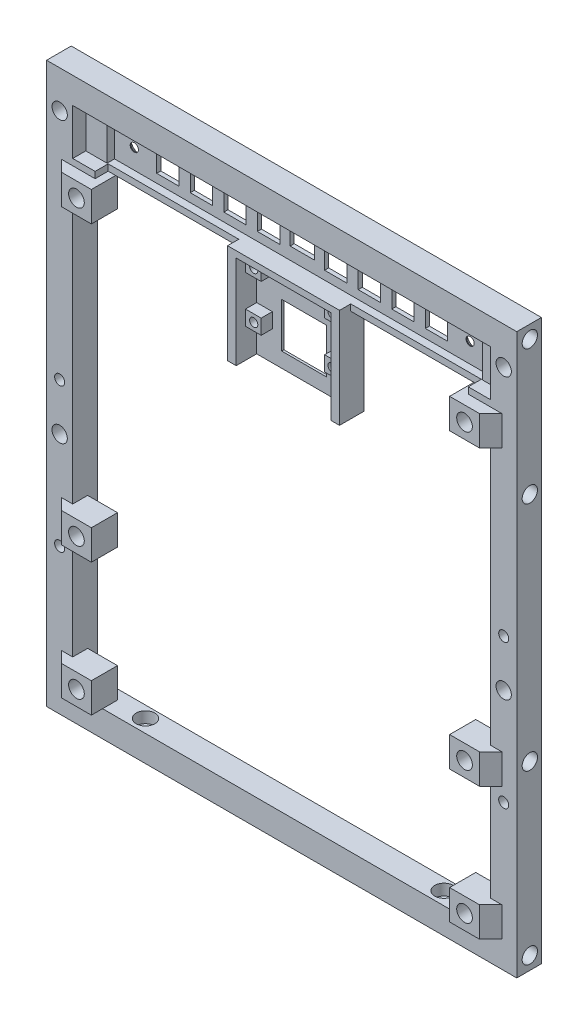
SolidWorks part; units mm, degrees
ref_plane "Front Plane" through (0, 0, 0) normal (0, 0, 1) x (1, 0, 0)
ref_plane "Top Plane" through (0, 0, 0) normal (0, 1, 0) x (1, 0, 0)
ref_plane "Right Plane" through (0, 0, 0) normal (1, 0, 0) x (0, 0, -1)
sketch "Sketch1" plane through (0, 0, 0) normal (0, 0, 1) x (1, 0, 0)
  line L1 (-63, -75) -> (63, -75)
  line L2 (-63, -75) -> (-63, 75)
  line L3 (-63, 75) -> (63, 75)
  line L4 (63, -75) -> (63, 75)
  line L5 (-63, -75) -> (63, 75) construction
  line L6 (-63, 75) -> (63, -75) construction
  line L7 (-56, -68) -> (56, -68)
  line L8 (-56, -68) -> (-56, 68)
  line L9 (-56, 68) -> (56, 68)
  line L10 (56, -68) -> (56, 68)
  line L11 (-56, -68) -> (56, 68) construction
  line L12 (-56, 68) -> (56, -68) construction
  point P0 (0, 0)
  point P6 (0, 0)
  dimension "D1" = 126
  dimension "D2" = 150
  dimension "D3" = 7
  dimension "D4" = 7
extrude "Boss-Extrude1" add sketch "Sketch1" along normal blind 7
sketch "Sketch2" plane through (-63, 0, 0) normal (-1, 0, 0) x (0, 0, 1)
  line L0 (3.5, 71.5) -> (3.5, -71.5) construction
  line L1 (7, 75) -> (0, 75) construction
  circle A0 centre (3.5, -71.5) radius 2.05
  circle A2 centre (3.5, 71.5) radius 2.05
  circle A3 centre (3.5, 35.5) radius 2.05
  circle A4 centre (3.5, -26.5) radius 2.05
  point P2 (3.5, 0)
  point P7 (3.5, 75)
  dimension "D2" = 4.1
  dimension "D3" = 36
  dimension "D4" = 45
  dimension "D1" = 3.5
extrude "Cut-Extrude1" cut sketch "Sketch2" against normal blind 6
mirror "Mirror1" about plane through (0, 0, 0) normal (1, 0, 0) of "Cut-Extrude1"
sketch "Sketch3" plane through (0, -68, 0) normal (0, 1, 0) x (1, 0, 0)
  line L0 (0, 0) -> (0, -7) construction
  line L1 (-56, 0) -> (56, 0) construction
  line L2 (-56, -7) -> (56, -7) construction
  line L3 (40, -3.5) -> (-40, -3.5) construction
  circle A0 centre (40, -3.5) radius 1.35
  circle A1 centre (-40, -3.5) radius 1.35
  point P9 (0, -3.5)
  dimension "D1" = 2.7
  dimension "D2" = 80
extrude "Cut-Extrude2" cut sketch "Sketch3" against normal through all
sketch "Sketch4" plane through (0, -68, 0) normal (0, 1, 0) x (1, 0, 0)
  circle A0 centre (40, -3.5) radius 2.5
  circle A1 centre (-40, -3.5) radius 2.5
  dimension "D1" = 5
extrude "Cut-Extrude3" cut sketch "Sketch4" against normal blind 3
sketch "Sketch5" plane through (0, 0, 0) normal (0, 0, -1) x (-1, 0, 0)
  line L0 (-59.5, -75) -> (-59.5, 75) construction
  line L1 (63, -75) -> (-63, -75) construction
  line L2 (-63, 75) -> (63, 75) construction
  line L3 (-56, 0) -> (-63, 0) construction
  line L4 (-56, -68) -> (-56, 68) construction
  line L5 (-63, -75) -> (-63, 75) construction
  line L6 (0, 75) -> (0, -75) construction
  line L7 (56, -68) -> (-56, -68) construction
  circle A0 centre (-59.5, 2.6) radius 1.35
  circle A1 centre (59.5, 2.6) radius 1.35
  circle A2 centre (-59.5, -36) radius 1.35
  circle A3 centre (59.5, -36) radius 1.35
  point P12 (-59.5, 0)
  point P13 (-59.5, 0)
  dimension "D1" = 2.7
  dimension "D2" = 2.6
  dimension "D3" = 32
extrude "Cut-Extrude4" cut sketch "Sketch5" against normal through all
sketch "Sketch6" plane through (0, 0, 0) normal (0, 0, -1) x (-1, 0, 0)
  circle A0 centre (-59.5, 2.6) radius 2.5
  circle A1 centre (59.5, 2.6) radius 2.5
  circle A2 centre (-59.5, -36) radius 2.5
  circle A3 centre (59.5, -36) radius 2.5
  dimension "D1" = 5
extrude "Cut-Extrude5" cut sketch "Sketch6" against normal blind 3
sketch "Sketch7" plane through (0, 0, 0) normal (0, 0, -1) x (-1, 0, 0)
  line L0 (-56, 68) -> (-63, 68) construction
  line L1 (-63, -75) -> (-63, 75) construction
  line L2 (-59.5, 65) -> (-59.5, -10) construction
  line L3 (-63, 75) -> (63, 75) construction
  circle A0 centre (-59.5, 65) radius 2.05
  circle A1 centre (-59.5, -10) radius 2.05
  point P8 (-59.5, 68)
  dimension "D1" = 4.1
  dimension "D2" = 10
  dimension "D3" = 75
extrude "Cut-Extrude6" cut sketch "Sketch7" against normal through all
mirror "Mirror2" about plane through (0, 0, 0) normal (1, 0, 0) of "Cut-Extrude6"
sketch "Sketch8" plane through (0, 0, 3) normal (0, 0, -1) x (-1, 0, 0)
  line L2 (-60.85, 0.4958) -> (-60.85, 4.7042)
  line L4 (-58.15, 0.4958) -> (-58.15, 4.7042)
  line L5 (-60.85, 0.4958) -> (-58.15, 4.7042) construction
  line L6 (-60.85, 4.7042) -> (-58.15, 0.4958) construction
  line L8 (-60.85, -38.1042) -> (-60.85, -33.8958)
  line L10 (-58.15, -38.1042) -> (-58.15, -33.8958)
  line L11 (-60.85, -38.1042) -> (-58.15, -33.8958) construction
  line L12 (-60.85, -33.8958) -> (-58.15, -38.1042) construction
  circle A0 centre (-59.5, 2.6) radius 2.5 construction
  circle A1 centre (-59.5, -36) radius 2.5 construction
  circle A2 centre (-59.5, -36) radius 2.5 construction
  arc A3 (-58.15, 4.7042) -> (-60.85, 4.7042) centre (-59.5, 2.6) ccw
  arc A4 (-58.15, -33.8958) -> (-60.85, -33.8958) centre (-59.5, -36) ccw
  circle A5 centre (-59.5, 2.6) radius 1.35 construction
  circle A6 centre (-59.5, -36) radius 1.35 construction
  arc A7 (-60.85, -38.1042) -> (-58.15, -38.1042) centre (-59.5, -36) ccw
  arc A8 (-60.85, 0.4958) -> (-58.15, 0.4958) centre (-59.5, 2.6) ccw
  point P0 (-59.5, 2.6)
  point P8 (-59.5, -36)
extrude "Cut-Extrude7" cut sketch "Sketch8" against normal blind 0.2
sketch "Sketch9" plane through (0, 0, 3.2) normal (0, 0, -1) x (-1, 0, 0)
  line L0 (-58.15, 2.6) -> (-58.15, 4.7042) construction
  line L1 (-60.85, 1.25) -> (-58.15, 1.25)
  line L2 (-60.85, 1.25) -> (-60.85, 3.95)
  line L3 (-60.85, 3.95) -> (-58.15, 3.95)
  line L4 (-58.15, 1.25) -> (-58.15, 3.95)
  line L5 (-60.85, 1.25) -> (-58.15, 3.95) construction
  line L6 (-60.85, 3.95) -> (-58.15, 1.25) construction
  line L7 (-58.15, -38.1042) -> (-58.15, -33.8958) construction
  line L8 (-60.85, -37.35) -> (-58.15, -37.35)
  line L9 (-60.85, -37.35) -> (-60.85, -34.65)
  line L10 (-60.85, -34.65) -> (-58.15, -34.65)
  line L11 (-58.15, -37.35) -> (-58.15, -34.65)
  line L12 (-60.85, -37.35) -> (-58.15, -34.65) construction
  line L13 (-60.85, -34.65) -> (-58.15, -37.35) construction
  arc A0 (-58.15, 2.6) -> (-60.85, 2.6) centre (-59.5, 2.6) ccw construction
  point P0 (-59.5, 2.6)
  point P8 (-59.5, -36)
extrude "Cut-Extrude8" cut sketch "Sketch9" against normal blind 0.2
mirror "Mirror3" about plane through (0, 0, 0) normal (1, 0, 0) of "Cut-Extrude8", "Cut-Extrude7"
sketch "Sketch10" plane through (0, 0, 7) normal (0, 0, 1) x (1, 0, 0)
  line L0 (56, -68) -> (56, 68) construction
  line L1 (56, -68) -> (50, -68)
  line L2 (56, -68) -> (56, -62)
  line L3 (56, -62) -> (50, -62)
  line L4 (50, -68) -> (50, -62)
  line L5 (56, -38.5) -> (50, -38.5)
  line L6 (56, -38.5) -> (56, -32.5)
  line L7 (56, -32.5) -> (50, -32.5)
  line L8 (50, -38.5) -> (50, -32.5)
  line L9 (-56, -68) -> (56, -68) construction
  dimension "D1" = 6
  dimension "D2" = 35.5
extrude "Boss-Extrude2" add sketch "Sketch10" against normal offset from surface (5.5 mm away) 1.5 up to face at (-57.45, -10, 0)
sketch "Sketch11" plane through (0, 0, 1.5) normal (0, 0, -1) x (-1, 0, 0)
  line L0 (-56, -38.5) -> (-50, -32.5) construction
  line L2 (-56, -68) -> (-50, -62) construction
  circle A0 centre (-53, -35.5) radius 1.65
  circle A1 centre (-53, -65) radius 1.65
  dimension "D1" = 3.3
extrude "Cut-Extrude9" cut sketch "Sketch11" against normal through all
mirror "Mirror4" about plane through (0, 0, 0) normal (1, 0, 0) of "Cut-Extrude9", "Boss-Extrude2"
sketch "Sketch12" plane through (0, 0, 0) normal (0, 0, -1) x (-1, 0, 0)
  line L0 (56, 68) -> (56, -68) construction
  line L1 (-56, 68) -> (56, 68)
  line L2 (-56, 68) -> (-56, 54)
  line L3 (-56, 54) -> (56, 54)
  line L4 (56, 68) -> (56, 54)
  dimension "D1" = 14
extrude "Boss-Extrude3" add sketch "Sketch12" against normal blind 1.5
sketch "Sketch13" plane through (0, 0, 1.5) normal (0, 0, 1) x (1, 0, 0)
  line L0 (-56, 68) -> (56, 54) construction
  line L2 (-50.3, 55.7) -> (50.3, 55.7)
  line L3 (-50.3, 55.7) -> (-50.3, 66.3)
  line L4 (-50.3, 66.3) -> (50.3, 66.3)
  line L5 (50.3, 55.7) -> (50.3, 66.3)
  line L6 (-50.3, 55.7) -> (50.3, 66.3) construction
  line L7 (-50.3, 66.3) -> (50.3, 55.7) construction
  line L8 (-56, 54) -> (56, 54)
  line L9 (-56, 54) -> (-56, 68)
  line L10 (-56, 68) -> (56, 68)
  line L11 (56, 54) -> (56, 68)
  line L12 (-56, 54) -> (56, 68) construction
  line L13 (-56, 68) -> (56, 54) construction
  point P4 (0, 61)
  point P9 (0, 61)
  dimension "D1" = 100.6
  dimension "D2" = 10.6
extrude "Boss-Extrude4" add sketch "Sketch13" along normal blind 2
sketch "Sketch14" plane through (0, 0, 1.5) normal (0, 0, 1) x (1, 0, 0)
  line L0 (0, 66.3) -> (0, 55.7) construction
  line L1 (50.3, 66.3) -> (-50.3, 66.3) construction
  line L2 (-50.3, 55.7) -> (50.3, 55.7) construction
  line L3 (-50.3, 61) -> (50.3, 61) construction
  line L4 (50.3, 55.7) -> (50.3, 66.3) construction
  line L5 (-33, 64) -> (-39, 64)
  line L6 (-3.25, 59) -> (3.25, 59)
  line L7 (-3.25, 59) -> (-3.25, 63)
  line L8 (-3.25, 63) -> (3.25, 63)
  line L9 (3.25, 59) -> (3.25, 63)
  line L10 (-3.25, 59) -> (3.25, 63) construction
  line L11 (-3.25, 63) -> (3.25, 59) construction
  line L12 (6, 58) -> (12, 58)
  line L13 (6, 58) -> (6, 64)
  line L14 (6, 64) -> (12, 64)
  line L15 (12, 58) -> (12, 64)
  line L16 (6, 58) -> (12, 64) construction
  line L17 (6, 64) -> (12, 58) construction
  line L18 (15, 58) -> (21, 58)
  line L19 (15, 58) -> (15, 64)
  line L20 (15, 64) -> (21, 64)
  line L21 (21, 58) -> (21, 64)
  line L22 (15, 58) -> (21, 64) construction
  line L23 (15, 64) -> (21, 58) construction
  line L24 (24, 58) -> (30, 58)
  line L25 (24, 58) -> (24, 64)
  line L26 (24, 64) -> (30, 64)
  line L27 (30, 58) -> (30, 64)
  line L28 (24, 58) -> (30, 64) construction
  line L29 (24, 64) -> (30, 58) construction
  line L30 (33, 58) -> (39, 58)
  line L31 (33, 58) -> (33, 64)
  line L32 (33, 64) -> (39, 64)
  line L33 (39, 58) -> (39, 64)
  line L34 (33, 58) -> (39, 64) construction
  line L35 (33, 64) -> (39, 58) construction
  line L36 (-39, 58) -> (-39, 64)
  line L37 (-33, 58) -> (-39, 58)
  line L38 (-33, 58) -> (-33, 64)
  line L39 (-24, 64) -> (-30, 64)
  line L40 (-30, 58) -> (-30, 64)
  line L41 (-24, 58) -> (-30, 58)
  line L42 (-24, 58) -> (-24, 64)
  line L43 (-15, 64) -> (-21, 64)
  line L44 (-21, 58) -> (-21, 64)
  line L45 (-15, 58) -> (-21, 58)
  line L46 (-15, 58) -> (-15, 64)
  line L47 (-6, 64) -> (-12, 64)
  line L48 (-12, 58) -> (-12, 64)
  line L49 (-6, 58) -> (-12, 58)
  line L50 (-6, 58) -> (-6, 64)
  circle A0 centre (-45, 61) radius 1.3 construction
  circle A1 centre (45, 61) radius 1.3 construction
  point P6 (0, 61)
  point P11 (0, 61)
  point P16 (9, 61)
  point P21 (18, 61)
  point P26 (27, 61)
  point P31 (36, 61)
  dimension "D10" = 2.6
  dimension "D9" = 45
  dimension "D1" = 6.5
  dimension "D2" = 4
  dimension "D3" = 6
  dimension "D4" = 9
  dimension "D5" = 9
  dimension "D6" = 9
  dimension "D7" = 9
  dimension "D8" = 45
extrude "Cut-Extrude10" cut sketch "Sketch14" against normal through all
sketch "Sketch15" plane through (0, 0, 1.5) normal (0, 0, 1) x (1, 0, 0)
  circle A0 centre (-45, 61) radius 1
  circle A1 centre (45, 61) radius 1
  dimension "D1" = 2
extrude "Boss-Extrude5" add sketch "Sketch15" along normal up to surface (2 mm away) up to face at (0, 61, 3.5)
chamfer "Chamfer1" distance 0.4 angle 45 3 edges at (-56, -7, 0) (56, -7, 0) (0, -68, 0) tangent propagation no
chamfer "Chamfer2" distance 0.4 angle 45 4 edges at (0, 75, 0) (-63, 0, 0) (0, -75, 0) (63, 0, 0)
chamfer "Chamfer3" distance 0.4 angle 45 36 edges at (-36, 58, 0) (-39, 61, 0) (-36, 64, 0) (-33, 61, 0) (-27, 58, 0) (-30, 61, 0) (-27, 64, 0) (-24, 61, 0) (-18, 58, 0) (-21, 61, 0) (-18, 64, 0) (-15, 61, 0) (-9, 58, 0) (-12, 61, 0) (-9, 64, 0) (-6, 61, 0) (0, 59, 0) (-3.25, 61, 0) (0, 63, 0) (3.25, 61, 0) (9, 58, 0) (6, 61, 0) (9, 64, 0) (12, 61, 0) (18, 58, 0) (15, 61, 0) (18, 64, 0) (21, 61, 0) (36, 58, 0) (33, 61, 0) (36, 64, 0) (39, 61, 0) (27, 58, 0) (24, 61, 0) (27, 64, 0) (30, 61, 0)
sketch "Sketch16" plane through (0, 0, 7) normal (0, 0, 1) x (1, 0, 0)
  line L0 (-50, 54) -> (-50, 55.7)
  line L1 (-56, -32.5) -> (-50, -32.5)
  line L2 (-56, -32.5) -> (-56, -26.5)
  line L3 (-56, -26.5) -> (-50, -26.5)
  line L4 (-50, -32.5) -> (-50, -26.5)
  line L5 (56, -32.5) -> (50, -32.5)
  line L6 (56, -32.5) -> (56, -26.5)
  line L7 (56, -26.5) -> (50, -26.5)
  line L8 (50, -32.5) -> (50, -26.5)
  line L9 (56, 54) -> (50, 54) construction
  line L10 (56, 54) -> (56, 48)
  line L11 (56, 48) -> (50, 48)
  line L12 (50, 54) -> (50, 48)
  line L13 (-56, 54) -> (-50, 54) construction
  line L14 (-56, 54) -> (-56, 48)
  line L15 (-56, 48) -> (-50, 48)
  line L16 (-50, 54) -> (-50, 48)
  line L17 (-50.3, 55.7) -> (50.3, 55.7) construction
  line L18 (-50, 55.7) -> (-56, 55.7)
  line L19 (-56, 68) -> (-56, 54) construction
  line L20 (-56, 55.7) -> (-56, 54)
  line L21 (50, 54) -> (50, 55.7)
  line L22 (50, 55.7) -> (56, 55.7)
  line L23 (56, 54) -> (56, 68) construction
  line L24 (56, 55.7) -> (56, 54)
  dimension "D1" = 6
extrude "Boss-Extrude7" add sketch "Sketch16" against normal offset from surface (5.5 mm away) 1.5 up to face at (-36, 61, 0)
sketch "Sketch17" plane through (0, 0, 1.5) normal (0, 0, -1) x (-1, 0, 0)
  line L0 (-50, 48) -> (50, -26.5) construction
  line L1 (-50, -26.5) -> (-50, -38.5) construction
  line L2 (-53, -29.5) -> (53, -29.5) construction
  line L3 (-53, -29.5) -> (-53, 51) construction
  line L4 (-53, 51) -> (53, 51) construction
  line L5 (53, -29.5) -> (53, 51) construction
  line L6 (-53, -29.5) -> (53, 51) construction
  line L7 (-53, 51) -> (53, -29.5) construction
  line L8 (50, -26.5) -> (56, -26.5) construction
  circle A0 centre (-53, -29.5) radius 1.65
  circle A1 centre (53, -29.5) radius 1.65
  circle A2 centre (53, 51) radius 1.65
  circle A3 centre (-53, 51) radius 1.65
  point P4 (0, 10.75)
  dimension "D3" = 3.3
  dimension "D1" = 3
  dimension "D2" = 3
extrude "Cut-Extrude11" cut sketch "Sketch17" against normal through all
sketch "Sketch18" plane through (0, 0, 1.5) normal (0, 0, 1) x (1, 0, 0)
  circle A0 centre (-45, 61) radius 1.1
  circle A1 centre (45, 61) radius 1.1
  dimension "D1" = 2.2
extrude "Cut-Extrude12" cut sketch "Sketch18" against normal through all both and the other way through all
chamfer "Chamfer4" distance 1.3 angle 45 2 edges at (-43.9, 61, 0) (46.1, 61, 0)
sketch "Sketch19" plane through (0, 0, 1.5) normal (0, 0, -1) x (-1, 0, 0)
  line L1 (-56, -68) -> (56, -68)
  line L2 (-56, -68) -> (-56, 54)
  line L3 (-56, 54) -> (56, 54)
  line L4 (56, -68) -> (56, 54)
extrude "Cut-Extrude13" cut sketch "Sketch19" against normal through all
ref_plane "Plane1" through (0, 0, 3) normal (0, 0, 1) x (1, 0, 0)
sketch "Sketch20" plane through (0, 0, 3) normal (0, 0, 1) x (1, 0, 0)
  line L0 (56, 54) -> (56, -68) construction
  line L1 (56, -68) -> (48, -68)
  line L2 (56, -68) -> (56, -60)
  line L3 (56, -60) -> (48, -60)
  line L4 (48, -68) -> (48, -60)
  line L5 (56, 54) -> (48, 54)
  line L6 (56, 54) -> (56, 46)
  line L7 (56, 46) -> (48, 46)
  line L8 (48, 54) -> (48, 46)
  line L9 (56, -24.5) -> (48, -24.5)
  line L10 (56, -24.5) -> (56, -32.5)
  line L11 (56, -32.5) -> (48, -32.5)
  line L12 (48, -24.5) -> (48, -32.5)
  dimension "D1" = 8
  dimension "D2" = 27.5
extrude "Boss-Extrude8" add sketch "Sketch20" along normal blind 7
sketch "Sketch21" plane through (0, 0, 3) normal (0, 0, -1) x (-1, 0, 0)
  line L0 (-48, 54) -> (-56, 46) construction
  line L1 (-56, -60) -> (-48, -68) construction
  line L2 (-56, -24.5) -> (-48, -32.5) construction
  circle A0 centre (-52, 50) radius 2.1
  circle A1 centre (-52, -64) radius 2.1
  circle A2 centre (-52, -28.5) radius 2.1
  dimension "D1" = 4.2
extrude "Cut-Extrude14" cut sketch "Sketch21" against normal through all
mirror "Mirror5" about plane through (0, 0, 0) normal (1, 0, 0) of "Cut-Extrude14", "Boss-Extrude8"
chamfer "Chamfer5" distance 3 angle 45 6 edges at (-56, -64, 7) (56, -64, 7) (56, 50, 7) (-56, 50, 7) (-56, -28.5, 7) (56, -28.5, 7)
sketch "Sketch23" plane through (0, 0, 0) normal (0, 0, -1) x (-1, 0, 0)
  line L0 (-56.4, 54) -> (56.4, 54) construction
  line L1 (-15, 54) -> (15, 54)
  line L2 (-15, 54) -> (-15, 29)
  line L3 (-15, 29) -> (15, 29)
  line L4 (15, 54) -> (15, 29)
  point P6 (0, 29)
  dimension "D1" = 25
  dimension "D2" = 30
extrude "Boss-Extrude10" add sketch "Sketch23" against normal up to surface (3.5 mm away) up to face at (0, 54.5667, 3.5)
sketch "Sketch24" plane through (0, 0, 3.5) normal (0, 0, 1) x (1, 0, 0)
  line L0 (15, 29) -> (-15, 29) construction
  line L1 (-12.7, 29) -> (12.7, 29)
  line L2 (-12.7, 29) -> (-12.7, 54)
  line L3 (-12.7, 54) -> (12.7, 54)
  line L4 (12.7, 29) -> (12.7, 54)
  line L5 (-48, 54) -> (-15, 54) construction
  point P6 (0, 29)
  dimension "D1" = 25.4
extrude "Cut-Extrude15" cut sketch "Sketch24" against normal offset from surface (2.5 mm away) 1 up to face at (-47.4, 61, 0)
sketch "Sketch26" plane through (0, 0, 1) normal (0, 0, 1) x (1, 0, 0)
  line L0 (12.7, 54) -> (-12.7, 54) construction
  line L1 (-12.5, 53.4) -> (12.5, 53.4) construction
  line L2 (-12.5, 53.4) -> (-12.5, 29.538) construction
  line L3 (-12.5, 29.538) -> (12.5, 29.538) construction
  line L4 (12.5, 53.4) -> (12.5, 29.538) construction
  line L5 (0, 53.4) -> (0, 29.538) construction
  line L6 (-10.5, 51.4) -> (10.5, 51.4) construction
  line L7 (-10.5, 51.4) -> (-10.5, 38.9) construction
  line L8 (-10.5, 38.9) -> (10.5, 38.9) construction
  line L9 (10.5, 51.4) -> (10.5, 38.9) construction
  line L10 (12.7, 54) -> (-12.7, 54) construction
  line L11 (-5.4, 33.6) -> (5.4, 33.6) construction
  line L12 (-5.4, 33.6) -> (-5.4, 44.4) construction
  line L13 (-5.4, 44.4) -> (5.4, 44.4) construction
  line L14 (5.4, 33.6) -> (5.4, 44.4) construction
  line L15 (-5.4, 33.6) -> (5.4, 44.4) construction
  line L16 (-5.4, 44.4) -> (5.4, 33.6) construction
  circle A0 centre (-10.5, 51.4) radius 1.1 construction
  circle A1 centre (10.5, 51.4) radius 1.1 construction
  circle A2 centre (10.5, 38.9) radius 1.1 construction
  circle A3 centre (-10.5, 38.9) radius 1.1 construction
  point P4 (0, 53.4)
  point P7 (0, 54)
  point P12 (0, 51.4)
  point P19 (0, 39)
  dimension "D3" = 2.2
  dimension "D1" = 25
  dimension "D2" = 23.862
  dimension "D4" = 2
  dimension "D5" = 14.5
  dimension "D6" = 10.8
  dimension "D7" = 10.8
  dimension "D8" = 14.4
  dimension "D9" = 0.6
  dimension "D10" = 2
sketch "Sketch27" plane through (0, 0, 1) normal (0, 0, 1) x (1, 0, 0)
  line L0 (-12.7, 54) -> (-12.7, 29) construction
  line L1 (-12.7, 54) -> (-8.5, 54)
  line L2 (-12.7, 54) -> (-12.7, 49.4)
  line L3 (-12.7, 49.4) -> (-8.5, 49.4)
  line L4 (-8.5, 54) -> (-8.5, 49.4)
  line L5 (-12.7, 36.9) -> (-8.5, 36.9)
  line L6 (-12.7, 36.9) -> (-12.7, 40.9)
  line L7 (-12.7, 40.9) -> (-8.5, 40.9)
  line L8 (-8.5, 36.9) -> (-8.5, 40.9)
  line L9 (0, 54) -> (0, 29) construction
  line L10 (12.7, 54) -> (-12.7, 54) construction
  line L11 (-12.7, 29) -> (12.7, 29) construction
  line L12 (8.5, 36.9) -> (8.5, 40.9)
  line L13 (12.7, 40.9) -> (8.5, 40.9)
  line L14 (12.7, 36.9) -> (12.7, 40.9)
  line L15 (12.7, 36.9) -> (8.5, 36.9)
  line L16 (8.5, 54) -> (8.5, 49.4)
  line L17 (12.7, 49.4) -> (8.5, 49.4)
  line L18 (12.7, 54) -> (12.7, 49.4)
  line L19 (12.7, 54) -> (8.5, 54)
  dimension "D1" = 2
  dimension "D2" = 2
  dimension "D3" = 2
  dimension "D4" = 2
  dimension "D5" = 2
extrude "Boss-Extrude11" add sketch "Sketch27" along normal blind 3
sketch "Sketch28" plane through (0, 0, 1) normal (0, 0, 1) x (1, 0, 0)
  line L0 (-5.4, 44.4) -> (5.4, 44.4) construction
  line L1 (-6, 33) -> (6, 33)
  line L2 (-6, 33) -> (-6, 45)
  line L3 (-6, 45) -> (6, 45)
  line L4 (6, 33) -> (6, 45)
  line L5 (-6, 33) -> (6, 45) construction
  line L6 (-6, 45) -> (6, 33) construction
  line L7 (5.4, 33.6) -> (5.4, 44.4) construction
  point P0 (0, 39)
  dimension "D1" = 0.6
  dimension "D2" = 0.6
extrude "Cut-Extrude16" cut sketch "Sketch28" against normal through all
sketch "Sketch29" plane through (0, 0, 4) normal (0, 0, 1) x (1, 0, 0)
  circle A0 centre (-10.5, 38.9) radius 1.1
  circle A1 centre (-10.5, 51.4) radius 1.1
  circle A2 centre (10.5, 51.4) radius 1.1
  circle A3 centre (10.5, 38.9) radius 1.1
  dimension "D1" = 2.2
extrude "Cut-Extrude17" cut sketch "Sketch29" against normal through all
chamfer "Chamfer6" distance 1.3 angle 45 4 edges at (11.6, 38.9, 0) (-9.4, 38.9, 0) (-9.4, 51.4, 0) (11.6, 51.4, 0)
chamfer "Chamfer7" distance 0.4 angle 45 4 edges at (0, 33, 0) (-6, 39, 0) (0, 45, 0) (6, 39, 0)
chamfer "Chamfer8" distance 0.4 angle 45 2 edges at (-35.7, 54, 0) (35.7, 54, 0)
sketch "Sketch30" plane through (0, 0, 3.5) normal (0, 0, 1) x (1, 0, 0)
  line L0 (-12.7, 29) -> (-12.7, 54)
  line L1 (-12.7, 54) -> (12.7, 54)
  line L2 (12.7, 54) -> (12.7, 29)
  line L3 (12.7, 29) -> (15, 29)
  line L4 (15, 29) -> (15, 55.7)
  line L5 (-50.3, 55.7) -> (50.3, 55.7) construction
  line L6 (15, 55.7) -> (-15, 55.7)
  line L7 (-15, 55.7) -> (-15, 29)
  line L8 (-12.7, 29) -> (-15, 29)
extrude "Boss-Extrude12" add sketch "Sketch30" along normal blind 3
